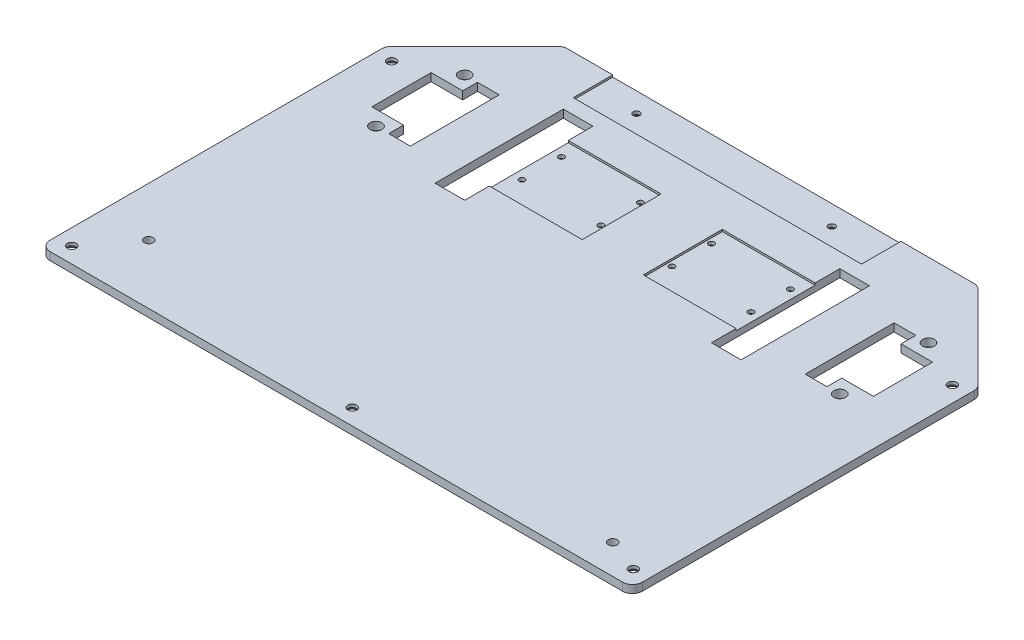
SolidWorks part; units mm, degrees
material "Acier non allié"
ref_plane "Front" through (0, 0, 0) normal (0, 0, 1) x (1, 0, 0)
ref_plane "Top" through (0, 0, 0) normal (0, 1, 0) x (1, 0, 0)
ref_plane "Right" through (0, 0, 0) normal (1, 0, 0) x (0, 0, -1)
sketch "Main scetch" plane through (0, 0, 0) normal (0, 1, 0) x (1, 0, 0)
  line L0 (-150, 0) -> (150, 0)
  line L1 (0, 0) -> (150, 0) construction
  line L2 (0, 0) -> (0, 220) construction
  line L3 (0, 220) -> (150, 220) construction
  line L4 (150, 0) -> (150, 220) construction
  line L5 (150, 0) -> (150, 175)
  line L6 (150, 175) -> (105, 220)
  line L10 (105, 220) -> (-105, 220)
  line L11 (-150, 0) -> (-150, 175)
  line L12 (-150, 175) -> (-105, 220)
  dimension "D1" = 150
  dimension "D2" = 220
  dimension "D3" = 45
  dimension "D4" = 45
extrude "Main extrusion" add sketch "Main scetch" along normal blind 4
fillet "Corner leave" radius 5 6 edges at (-150, 2, 0) (150, 2, -175) (105, 2, -220) (150, 2, 0) (-105, 2, -220) (-150, 2, -175)
sketch "Esquisse2" plane through (0, 4, 0) normal (0, 1, 0) x (1, 0, 0)
  line L0 (-145, 0) -> (145, 0) construction
  line L1 (150, 5) -> (150, 172.9289) construction
  line L2 (148.5355, 176.4645) -> (106.4645, 218.5355) construction
  line L3 (102.9289, 220) -> (-102.9289, 220) construction
  line L4 (-106.4645, 218.5355) -> (-148.5355, 176.4645) construction
  line L5 (-150, 172.9289) -> (-150, 5) construction
  line L6 (-145, 0) -> (145, 0) construction
  line L7 (150, 5) -> (150, 172.9289) construction
  line L8 (148.5355, 176.4645) -> (106.4645, 218.5355) construction
  line L9 (102.9289, 220) -> (-102.9289, 220) construction
  line L10 (-106.4645, 218.5355) -> (-148.5355, 176.4645) construction
  line L11 (-150, 172.9289) -> (-150, 5) construction
  line L12 (0, 0) -> (0, 238.9669) construction
  line L13 (0, 160) -> (165.6987, 160) construction
  line L14 (70, 230.4421) -> (70, 102.0601) construction
  line L15 (62.5, 192.5) -> (77.5, 192.5)
  line L16 (62.5, 192.5) -> (62.5, 127.5)
  line L17 (62.5, 127.5) -> (77.5, 127.5)
  line L18 (77.5, 192.5) -> (77.5, 127.5)
  line L19 (100, 137.5) -> (100, 182.5)
  line L20 (100, 182.5) -> (111, 182.5)
  line L22 (127, 175) -> (127, 145)
  line L23 (100, 137.5) -> (111, 137.5)
  line L35 (111, 182.5) -> (111, 175)
  line L36 (111, 175) -> (127, 175)
  line L37 (111, 137.5) -> (111, 145)
  line L38 (111, 145) -> (127, 145)
  line L39 (-111, 137.5) -> (-111, 145)
  line L40 (-100, 137.5) -> (-111, 137.5)
  line L41 (-100, 137.5) -> (-100, 182.5)
  line L42 (-100, 182.5) -> (-111, 182.5)
  line L43 (-111, 182.5) -> (-111, 175)
  line L44 (-111, 175) -> (-127, 175)
  line L45 (-127, 175) -> (-127, 145)
  line L46 (-111, 145) -> (-127, 145)
  line L47 (-62.5, 127.5) -> (-77.5, 127.5)
  line L48 (-77.5, 192.5) -> (-77.5, 127.5)
  line L49 (-62.5, 192.5) -> (-77.5, 192.5)
  line L50 (-62.5, 192.5) -> (-62.5, 127.5)
  circle A0 centre (117.47, 182.47) radius 3
  circle A1 centre (117.47, 137.53) radius 3
  circle A2 centre (-117.47, 137.53) radius 3
  circle A3 centre (-117.47, 182.47) radius 3
  point P28 (127, 160)
  point P29 (100, 160)
  dimension "D12" = 6
  dimension "D1" = 60
  dimension "D2" = 65
  dimension "D3" = 70
  dimension "D4" = 15
  dimension "D5" = 27
  dimension "D6" = 45
  dimension "D7" = 100
  dimension "D8" = 11
  dimension "D9" = 30
  dimension "D10" = 17.47
  dimension "D11" = 22.47
extrude "Enlèv. mat.-Extru.1" cut sketch "Esquisse2" against normal through all
sketch "Esquisse8" plane through (0, 4, 0) normal (0, 1, 0) x (1, 0, 0)
  line L0 (-150, 172.9289) -> (-150, 5) construction
  line L1 (-145, 0) -> (145, 0) construction
  line L3 (150, 5) -> (150, 172.9289) construction
  circle A0 centre (-125, 30) radius 1.5
  circle A1 centre (125, 15) radius 1.5
  circle A2 centre (-125, 12.5) radius 1
  circle A3 centre (-125, 47.5) radius 1
  dimension "D1" = 3
  dimension "D4" = 3
  dimension "D6" = 25
  dimension "D7" = 2
  dimension "D8" = 2
  dimension "D2" = 25
  dimension "D3" = 30
  dimension "D5" = 15
  dimension "D9" = 17.5
  dimension "D10" = 17.5
hole_wizard "Dégagement M41" positions "Esquisse16" profile "Esquisse17" hole size "M4" standard "ISO" end condition through all
sketch "Esquisse16" plane through (0, 4, 0) normal (0, 1, 0) x (1, 0, 0)
  point P0 (-125, 30)
  point P3 (125, 15)
sketch "Esquisse17" plane through (-125, 4, -30) normal (1, 0, 0) x (0, 0, 1)
  line L0 (0, 0) -> (0, 4)
  line L1 (0, 4) -> (2.25, 4)
  line L2 (2.25, 4) -> (2.25, 0)
  line L5 (2.25, 0) -> (0, 0)
  line L11 (0, -6.35) -> (0, 107.95) construction
  dimension "Diamètre du perçage jusqu'au prochain" = 4.5
  dimension "Profondeur du perçage jusqu'au prochain" = 4
sketch "Esquisse18" plane through (0, 4, 0) normal (0, 1, 0) x (1, 0, 0)
  line L0 (-150, 172.9289) -> (-150, 5) construction
  line L1 (-145, 0) -> (145, 0) construction
  line L3 (150, 5) -> (150, 172.9289) construction
  circle A0 centre (-142, 8) radius 1
  circle A1 centre (-142, 170) radius 1
  circle A4 centre (142, 170) radius 1
  circle A5 centre (142, 8) radius 1
  circle A6 centre (0, 8) radius 1.5
  dimension "D1" = 2
  dimension "D2" = 2
  dimension "D3" = 3
  dimension "D4" = 8
  dimension "D5" = 2
  dimension "D6" = 2
  dimension "D7" = 8
  dimension "D8" = 8
  dimension "D9" = 170
  dimension "D10" = 8
  dimension "D15" = 8
  dimension "D16" = 170
  dimension "D17" = 8
  dimension "D18" = 8
sketch "Esquisse23" plane through (0, 4, 0) normal (0, 1, 0) x (1, 0, 0)
  line L0 (-62.5, 127.5) -> (-62.5, 192.5) construction
  line L1 (-62.5, 180) -> (-15.5, 180)
  line L2 (-62.5, 180) -> (-62.5, 140)
  line L3 (-62.5, 140) -> (-15.5, 140)
  line L4 (-15.5, 180) -> (-15.5, 140)
  line L5 (102.9289, 220) -> (-102.9289, 220) construction
  dimension "D1" = 40
  dimension "D2" = 47
  dimension "D3" = 40
extrude "Enlèv. mat.-Extru.2" cut sketch "Esquisse23" against normal blind 1
sketch "Esquisse24" plane through (0, 3, 0) normal (0, 1, 0) x (1, 0, 0)
  line L0 (-58, 228.7511) -> (-58, 75.2489) construction
  line L1 (-62.5, 180) -> (-62.5, 140) construction
  line L2 (-15.5, 180) -> (-62.5, 180) construction
  line L3 (-18, 126.9657) -> (-18, 195.1017) construction
  line L4 (-58, 172) -> (-9.2469, 172) construction
  line L5 (-58, 152) -> (-13.1999, 152) construction
  circle A0 centre (-58, 172) radius 1
  circle A1 centre (-58, 152) radius 1
  circle A2 centre (-18, 172) radius 1
  circle A3 centre (-18, 152) radius 1
  dimension "D1" = 2
  dimension "D2" = 2
  dimension "D7" = 2
  dimension "D8" = 2
  dimension "D3" = 20
  dimension "D4" = 4.5
  dimension "D5" = 8
  dimension "D6" = 40
extrude "Enlèv. mat.-Extru.3" cut sketch "Esquisse24" against normal through all
hole_wizard "Fraisage pour vis à tête fraisée M2.51" positions "Esquisse27" profile "Esquisse28" countersink size "M2.5" standard "ISO" end condition through all
sketch "Esquisse27" plane through (0, 0, 0) normal (0, -1, 0) x (-1, 0, 0)
  point P0 (18, 172)
  point P3 (58, 172)
  point P6 (58, 152)
  point P9 (18, 152)
sketch "Esquisse28" plane through (-18, 0, -172) normal (1, 0, 0) x (0, 0, -1)
  line L0 (0, 0) -> (0, 4)
  line L1 (0, 4) -> (1.45, 4)
  line L2 (1.45, 4) -> (1.45, 1.3)
  line L3 (1.45, 1.3) -> (2.75, 0)
  line L5 (2.75, 0) -> (0, 0)
  line L6 (-1.45, 1.3) -> (-2.75, 0) construction
  line L11 (0, -6.35) -> (0, 107.95) construction
  dimension "Diamètre du perçage jusqu'au prochain" = 2.9
  dimension "Profondeur du perçage jusqu'au prochain" = 4
  dimension "Diamètre du fraisage entrant" = 5.5
  dimension "Angle du fraisage entrant" = 90
mirror "Symétrie1" about plane through (0, 0, 0) normal (1, 0, 0) of "Enlèv. mat.-Extru.3", "Fraisage pour vis à tête fraisée M2.51", "Enlèv. mat.-Extru.2"
hole_wizard "Fraisage pour vis à tête fraisée M41" positions "Esquisse30" profile "Esquisse31" countersink size "M4" standard "ISO" end condition through all
sketch "Esquisse30" plane through (0, 0, 0) normal (0, -1, 0) x (-1, 0, 0)
  point P0 (-142.0349, 8.4348)
  point P2 (0, 8.1016)
  point P4 (0, 8.1016)
  point P6 (142, 8)
  point P9 (142, 170)
  point P12 (-142, 170)
sketch "Esquisse31" plane through (142.0349, 0, -8.4348) normal (1, 0, 0) x (0, 0, -1)
  line L0 (0, 0) -> (0, 4)
  line L1 (0, 4) -> (2.25, 4)
  line L2 (2.25, 4) -> (2.25, 2.45)
  line L3 (2.25, 2.45) -> (4.7, 0)
  line L5 (4.7, 0) -> (0, 0)
  line L6 (-2.25, 2.45) -> (-4.7, 0) construction
  line L11 (0, -6.35) -> (0, 107.95) construction
  dimension "Diamètre du perçage jusqu'au prochain" = 4.5
  dimension "Profondeur du perçage jusqu'au prochain" = 4
  dimension "Diamètre du fraisage entrant" = 9.4
  dimension "Angle du fraisage entrant" = 90
sketch "Esquisse32" plane through (0, 4, 0) normal (0, 1, 0) x (1, 0, 0)
  line L0 (102.9289, 220) -> (-102.9289, 220) construction
  line L1 (-80, 220) -> (66, 220)
  line L2 (-80, 220) -> (-80, 200)
  line L3 (-80, 200) -> (66, 200)
  line L4 (66, 220) -> (66, 200)
  line L5 (150, 5) -> (150, 172.9289) construction
  dimension "D1" = 84
  dimension "D2" = 146
  dimension "D3" = 20
extrude "Enlèv. mat.-Extru.4" cut sketch "Esquisse32" against normal blind 1
sketch "Esquisse33" plane through (0, 0, 0) normal (0, -1, 0) x (1, 0, 0)
  line L4 (-80, -200) -> (-80, -220)
  line L5 (66, -200) -> (-80, -200)
  line L6 (66, -220) -> (66, -200)
  line L7 (-80, -220) -> (66, -220)
  line L8 (-80, -200) -> (-80, -220) construction
  line L9 (66, -200) -> (-80, -200) construction
  line L10 (66, -220) -> (66, -200) construction
  line L11 (-80, -220) -> (66, -220) construction
  circle A0 centre (-58, -210) radius 1
  circle A1 centre (41, -210) radius 1
  dimension "D4" = 2
  dimension "D7" = 2
  dimension "D2" = 22
  dimension "D3" = 10
  dimension "D5" = 25
  dimension "D6" = 10
  dimension "D1" = 0
extrude "Enlèv. mat.-Extru.5" cut sketch "Esquisse33" against normal through all
hole_wizard "Fraisage pour vis à tête fraisée M31" positions "Esquisse34" profile "Esquisse35" countersink size "M3" standard "ISO" end condition through all
sketch "Esquisse34" plane through (0, 0, 0) normal (0, -1, 0) x (-1, 0, 0)
  point P0 (58, 210)
  point P3 (-41, 210)
sketch "Esquisse35" plane through (-58, 0, -210) normal (1, 0, 0) x (0, 0, -1)
  line L0 (0, 0) -> (0, 4)
  line L1 (0, 4) -> (1.7, 4)
  line L2 (1.7, 4) -> (1.7, 1.45)
  line L3 (1.7, 1.45) -> (3.15, 0)
  line L5 (3.15, 0) -> (0, 0)
  line L6 (-1.7, 1.45) -> (-3.15, 0) construction
  line L11 (0, -6.35) -> (0, 107.95) construction
  dimension "Diamètre du perçage jusqu'au prochain" = 3.4
  dimension "Profondeur du perçage jusqu'au prochain" = 4
  dimension "Diamètre du fraisage entrant" = 6.3
  dimension "Angle du fraisage entrant" = 90
equation "\"WIDTH\"= 300mm'Total width of the robot"
equation "\"LENGTH\"= 220mm'Total length of the robot"
equation "\"D1@Main scetch\" = \"WIDTH\" / 2"
equation "\"D2@Main scetch\" = \"LENGTH\""
equation "\"CUT_DEPTH\"= 45mm'Depth of the cut on the edges of the plate"
equation "\"D3@Main scetch\" = \"CUT_DEPTH\""
equation "\"D4@Main scetch\" = \"CUT_DEPTH\""
equation "\"Plate_th\"= 3mm'Thickness of the plate"
equation "\"D1\"= \"Plate_th\""
